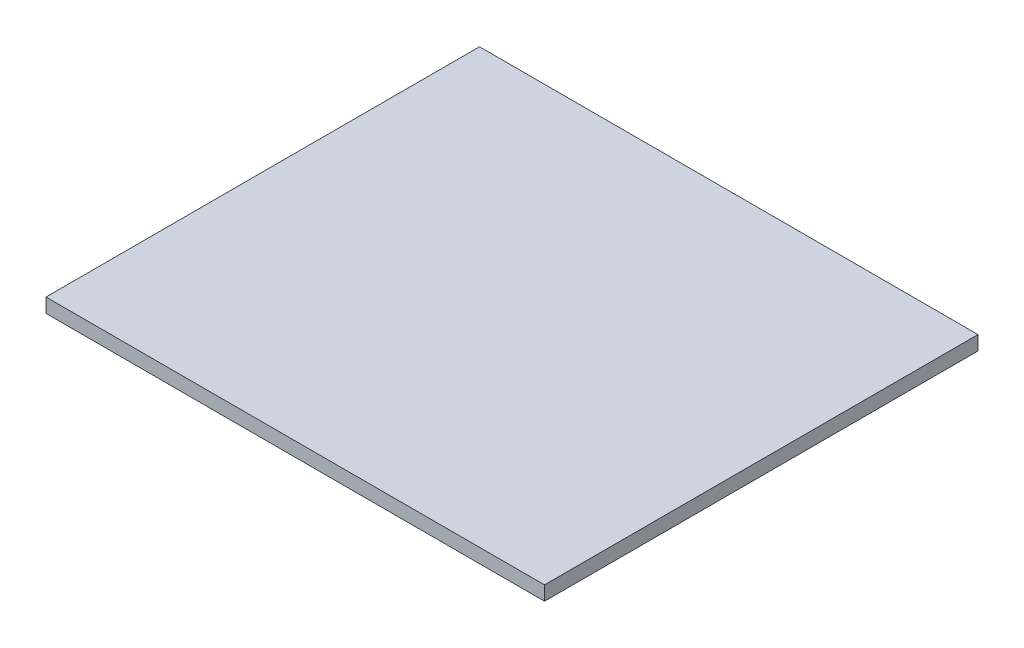
SolidWorks part; units mm, degrees
ref_plane "Front Plane" through (0, 0, 0) normal (0, 0, 1) x (1, 0, 0)
ref_plane "Top Plane" through (0, 0, 0) normal (0, 1, 0) x (1, 0, 0)
ref_plane "Right Plane" through (0, 0, 0) normal (1, 0, 0) x (0, 0, -1)
sketch "Sketch1" plane through (0, 0, 0) normal (0, 1, 0) x (1, 0, 0)
  line L1 (-44.5325, -38.7239) -> (44.5325, -38.7239)
  line L2 (-44.5325, -38.7239) -> (-44.5325, 38.7239)
  line L3 (-44.5325, 38.7239) -> (44.5325, 38.7239)
  line L4 (44.5325, -38.7239) -> (44.5325, 38.7239)
  line L5 (-44.5325, -38.7239) -> (44.5325, 38.7239) construction
  line L6 (-44.5325, 38.7239) -> (44.5325, -38.7239) construction
  point P0 (0, 0)
extrude "Boss-Extrude1" add sketch "Sketch1" along normal blind 2.54
